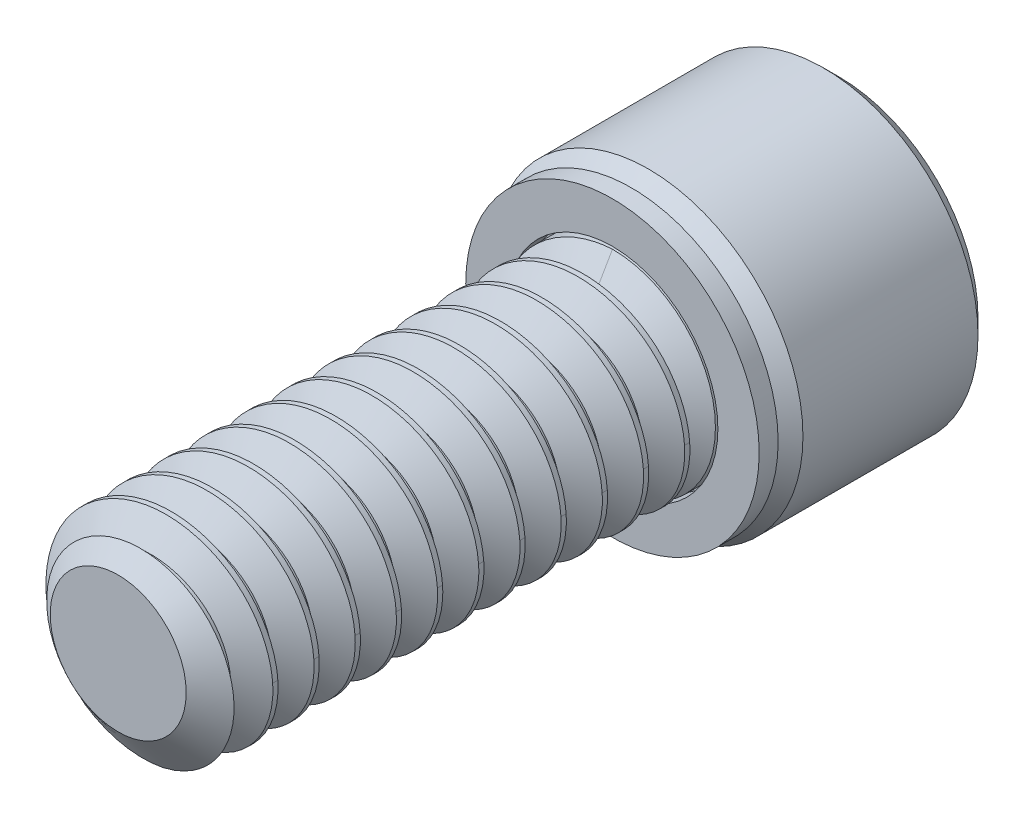
SolidWorks part; units mm, degrees
note: '?' marks a value the reader was unsure of.
other "DetailItem1"
ref_plane "Front Plane" through (0, 0, 0) normal (0, 0, 1) x (1, 0, 0)
ref_plane "Top Plane" through (0, 0, 0) normal (0, 1, 0) x (1, 0, 0)
ref_plane "Right Plane" through (0, 0, 0) normal (1, 0, 0) x (0, 0, -1)
sketch "Sketch1" plane through (0, 0, 0) normal (0, 0, 1) x (1, 0, 0)
  circle A0 centre (0, 0) radius 3.175
  dimension "OD" = 6.35
extrude "Extrude1" add sketch "Sketch1" against normal blind 15.875
sketch "Sketch2" plane through (0, 0, 0) normal (0, 0, 1) x (1, 0, 0)
  circle A0 centre (0, 0) radius 3.175 construction
  circle A1 centre (0, 0) radius 3.175
curve "Helix/Spiral1" pitch 1.27 height 17.145 turns 13.5 parameters "pitch"=1.27
sketch "Sketch3" plane through (0, 0, 0) normal (1, 0, 0) x (0, 0, -1)
  line L0 (-1.1112, 3.175) -> (-0.635, 2.3501)
  line L1 (-0.635, 2.3501) -> (-0.4763, 2.3501)
  line L2 (-0.4763, 2.3501) -> (0, 3.175)
  line L3 (-1.1112, 3.175) -> (0, 3.175)
  line L4 (-0.5556, 3.175) -> (-0.5556, 2.3501) construction
  line L5 (-0.8731, 2.7626) -> (-0.2381, 2.7626) construction
  line L6 (0, 3.175) -> (0, -3.175) construction
  dimension "D1" = 0.1588
  dimension "D2" = 0.635
  dimension "D3" = 60
sweep "Cut-Sweep1" cut profiles "Sketch3" path "Helix/Spiral1"
sketch "Sketch4" plane through (0, 0, 0) normal (1, 0, 0) x (0, 0, -1)
  line L0 (0.7554, 3.175) -> (0, 2.0961)
  line L1 (0, 2.0961) -> (0, 3.175)
  line L2 (0.7554, 3.175) -> (0, 3.175)
  line L3 (-1.1112, 3.175) -> (0, 3.175) construction
  line L4 (0, 0) -> (7.0209, 0) construction
  dimension "D1" = 55
  dimension "D2" = 0.254
revolve "Cut-Revolve1" cut sketch "Sketch4" angle 360 about L4
sketch "Sketch6" plane through (0, 0, -15.875) normal (0, 0, -1) x (-1, 0, 0)
  circle A0 centre (0, 0) radius 4.7625
  dimension "head dia" = 9.525
extrude "Extrude2" add sketch "Sketch6" along normal blind 6.35
sketch "Sketch7" plane through (0, 0, -22.225) normal (0, 0, -1) x (-1, 0, 0)
  line L1 (0, 2.7496) -> (-2.3813, 1.3748)
  line L2 (-2.3813, 1.3748) -> (-2.3813, -1.3748)
  line L3 (-2.3813, -1.3748) -> (0, -2.7496)
  line L4 (0, -2.7496) -> (2.3813, -1.3748)
  line L5 (2.3813, -1.3748) -> (2.3813, 1.3748)
  line L6 (2.3813, 1.3748) -> (0, 2.7496)
  circle A0 centre (0, 0) radius 2.3813 construction
  dimension "hex dia" = 4.7625
extrude "Cut-Extrude1" cut sketch "Sketch7" against normal blind 3.5719
sketch "Sketch8" plane through (0, 0, -22.225) normal (0, 0, -1) x (-1, 0, 0)
  circle A0 centre (0, 0) radius 2.7496
extrude "Cut-Extrude2" cut sketch "Sketch8" against normal through all draft 45
chamfer "Chamfer1" distance 0.4763 angle 45 2 edges at (-4.7625, 0, -22.225) (-4.7625, 0, -15.875)
sketch "Sketch10" plane through (0, 0, -15.875) normal (0, 0, 1) x (1, 0, 0)
  circle A1 centre (0, 0) radius 3.175
  circle A2 centre (0, 0) radius 3.175
  dimension "D1" = 0
ref_plane "Plane1" through (0, 0, 0) normal (0, 0, 1) x (1, 0, 0)
extrude "partial thread" [suppressed] add sketch "Sketch10" along normal up to surface (12.7 mm away) separate body
chamfer "Chamfer2" [suppressed] distance 0.127 angle 45
combine bodies "Combine1" [suppressed] operation type? add bodies to combine 107 108
sketch "Sketch9" plane through (0, 0, 0) normal (1, 0, 0) x (0, 0, -1)
  line L0 (0, 3.175) -> (0, -3.175) construction
  line L1 (3.175, 3.175) -> (3.175, -3.175) construction
  dimension "D1" = 3.175
sketch "Sketch11" plane through (0, 0, -15.875) normal (0, 0, 1) x (1, 0, 0)
  circle A1 centre (0, 0) radius 3.175
  circle A2 centre (0, 0) radius 3.175
  dimension "D1" = 0
extrude "Boss-Extrude1" add sketch "Sketch11" along normal blind 0.635 separate body
sketch "Sketch12" plane through (0, 0, -15.24) normal (0, 0, 1) x (1, 0, 0)
  circle A1 centre (0, 0) radius 3.175
  circle A2 centre (0, 0) radius 3.175
  dimension "D1" = 0
extrude "Boss-Extrude2" add sketch "Sketch12" along normal blind 2.54 draft 60
ref_plane "Plane2" through (0, 0, -15.8242) normal (0, 0, 1) x (1, 0, 0)
sketch "Sketch14" plane through (0, 0, -15.8242) normal (0, 0, 1) x (1, 0, 0)
  line L0 (0, 3.2512) -> (0, 4.2863) construction
  line L1 (0, 4.2863) -> (0, 4.7625) construction
  circle A1 centre (0, 0) radius 4.2863 construction
  circle A2 centre (0, 0) radius 3.2512
  circle A3 centre (0, 0) radius 3.2512
  circle A4 centre (0, 0) radius 4.7625 construction
  circle A5 centre (0, 0) radius 4.5244
  point P7 (0, 4.5244)
  dimension "D1" = 0.0762
extrude "Boss-Extrude3" add sketch "Sketch14" along normal up to vertex (0.5842 mm away) separate body
equation "\"D3@Helix/Spiral1\" = \"screw length@Extrude1\"+\"pitch@Helix/Spiral1\""
equation "\"D1@Sketch3\" = \"pitch@Helix/Spiral1\"*.125"
equation "\"D2@Sketch3\" = \"pitch@Helix/Spiral1\"*.5"
equation "\"D1@Cut-Extrude1\" = \"hex dia@Sketch7\"*.75"
equation "\"D1@Chamfer1\" = \"head dia@Sketch6\"*.05"
equation "\"D1@Sketch9\" = \"pitch@Helix/Spiral1\"*2.5"
equation "\"D1@Chamfer2\"=\"OD@Sketch1\"*.02"
equation "\"D1@Boss-Extrude1\" = \"pitch@Helix/Spiral1\" * .5"
